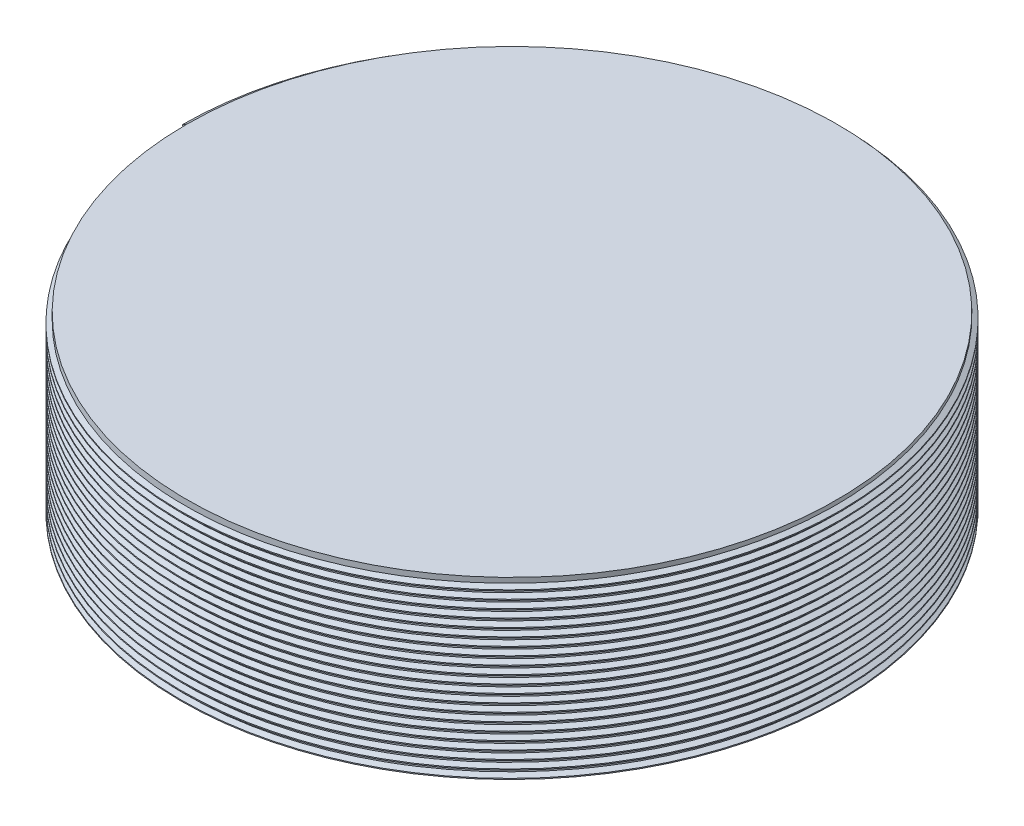
SolidWorks part; units mm, degrees
ref_plane "Front Plane" through (0, 0, 0) normal (0, 0, 1) x (1, 0, 0)
ref_plane "Top Plane" through (0, 0, 0) normal (0, 1, 0) x (1, 0, 0)
ref_plane "Right Plane" through (0, 0, 0) normal (1, 0, 0) x (0, 0, -1)
sketch "Sketch1" plane through (0, 0, 0) normal (0, 1, 0) x (1, 0, 0)
  circle A0 centre (0, 0) radius 23.9
  dimension "D1" = 47.8
extrude "Boss-Extrude1" add sketch "Sketch1" along normal blind 12.7
thread "MinColWidth_OnTracking1" pitch 0.6 method extrude profile "HeaderRowsCount1" start angle 0, offset 0, length 12.7, pitch 0.6, diameter 47.8
ref_plane "Plane1" through (-23.9, 12.7, 0) normal (0, 0, 1) x (-1, 0, 0)
sketch "HeaderRowsCount1" plane through (-23.9, 12.7, 0) normal (0, 0, 1) x (-1, 0, 0)
  line L0 (0, 0) -> (0, 0.6) construction
  line L1 (0, 0) -> (0.3248, 0.1875)
  line L2 (0.3248, 0.1875) -> (0.3248, 0.2625)
  line L3 (0.3248, 0.2625) -> (0, 0.45)
  line L4 (0.3248, 0.225) -> (0, 0.225) construction
  line L11 (0, 0) -> (0, 0.45)
  point P2 (0, 0)
  dimension "Pitch" = 0.6
  dimension "Profile_Angle" = 60
  dimension "Profile_Land" = 0.075
  dimension "Profile_Height" = 0.3248
